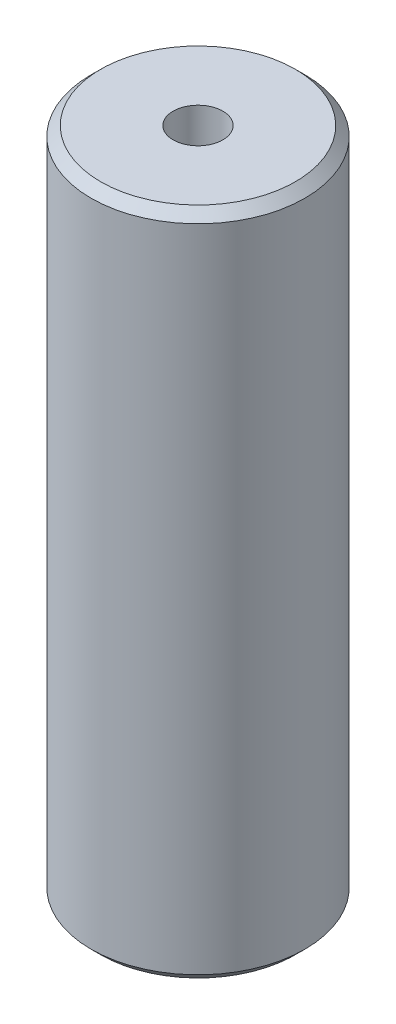
SolidWorks part; units mm, degrees
ref_plane "Front Plane" through (0, 0, 0) normal (0, 0, 1) x (1, 0, 0)
ref_plane "Top Plane" through (0, 0, 0) normal (0, 1, 0) x (1, 0, 0)
ref_plane "Right Plane" through (0, 0, 0) normal (1, 0, 0) x (0, 0, -1)
sketch "Sketch1" plane through (0, 0, 0) normal (0, 1, 0) x (1, 0, 0)
  circle A0 centre (0, 0) radius 5
  dimension "SHAFT_OD" = 10
extrude "Boss-Extrude1" add sketch "Sketch1" along normal blind 31.3022
sketch "Sketch2" plane through (0, 0, 0) normal (0, 1, 0) x (1, 0, 0)
  circle A0 centre (0, 0) radius 1.1644
  dimension "BORE_D" = 2.3288
extrude "Cut-Extrude1" cut sketch "Sketch2" along normal through all
chamfer "Chamfer1" distance 0.445 angle 45 2 edges at (0, 31.3022, 5) (0, 0, 5)
